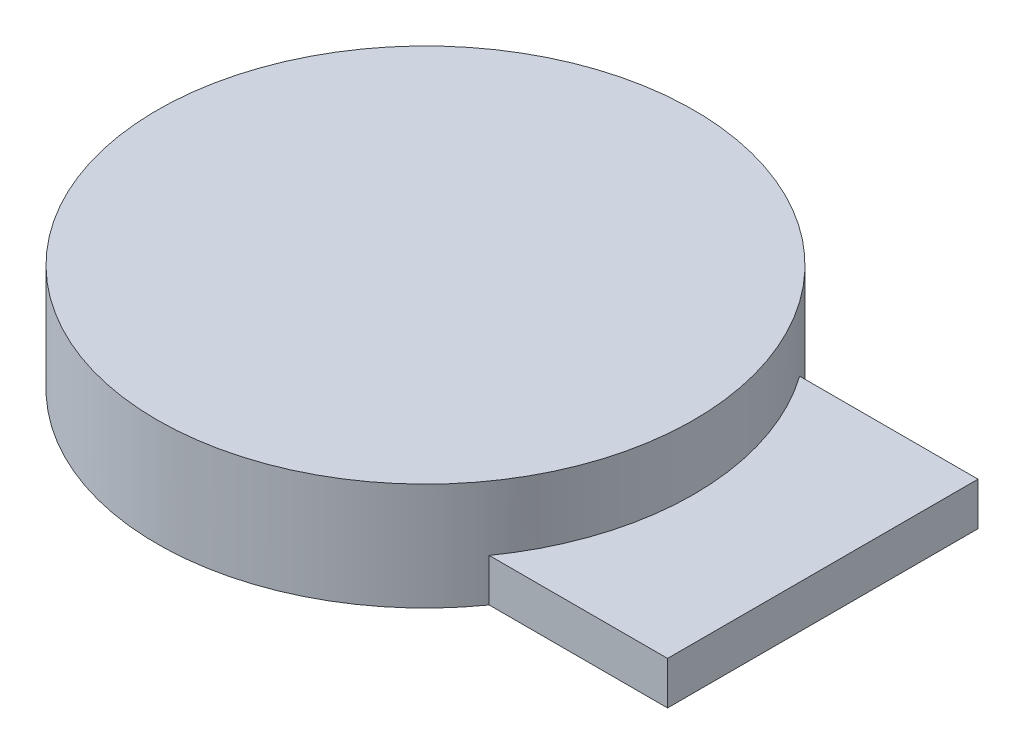
SolidWorks part; units mm, degrees
ref_plane "Front Plane" through (0, 0, 0) normal (0, 0, 1) x (1, 0, 0)
ref_plane "Top Plane" through (0, 0, 0) normal (0, 1, 0) x (1, 0, 0)
ref_plane "Right Plane" through (0, 0, 0) normal (1, 0, 0) x (0, 0, -1)
sketch "Sketch1" plane through (0, 0, 0) normal (0, 1, 0) x (1, 0, 0)
  circle A0 centre (0, 0) radius 15.875
  dimension "D1" = 31.75
extrude "Boss-Extrude1" add sketch "Sketch1" along normal blind 6.35
sketch "Sketch2" plane through (0, 0, 0) normal (0, -1, 0) x (1, 0, 0)
  line L1 (23.5014, 9.1826) -> (8.2486, 9.1826)
  line L2 (23.5014, 9.1826) -> (23.5014, -9.1826)
  line L3 (23.5014, -9.1826) -> (8.2486, -9.1826)
  line L4 (8.2486, 9.1826) -> (8.2486, -9.1826)
  line L5 (23.5014, 9.1826) -> (8.2486, -9.1826) construction
  line L6 (23.5014, -9.1826) -> (8.2486, 9.1826) construction
  circle A0 centre (0, 0) radius 15.875 construction
  point P0 (15.875, 0)
extrude "Boss-Extrude2" add sketch "Sketch2" against normal blind 2.54
